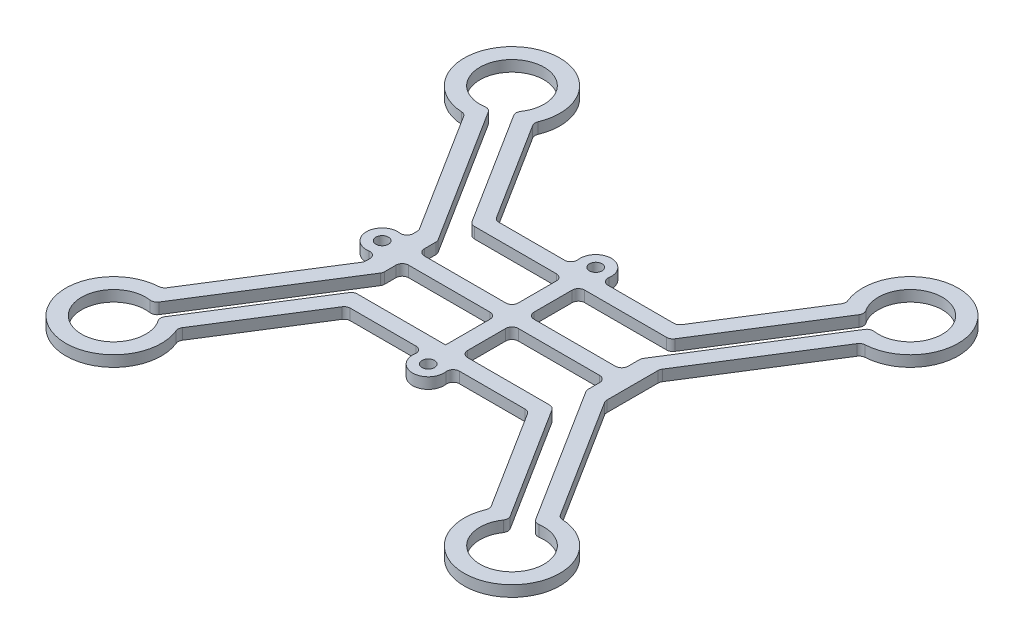
SolidWorks part; units mm, degrees
material "Hexcel AS4C (3000 Filaments)"
ref_plane "Front Plane" through (0, 0, 0) normal (0, 0, 1) x (1, 0, 0)
ref_plane "Top Plane" through (0, 0, 0) normal (0, 1, 0) x (1, 0, 0)
ref_plane "Right Plane" through (0, 0, 0) normal (1, 0, 0) x (0, 0, -1)
sketch "Sketch1" plane through (0, 0, 0) normal (0, 1, 0) x (1, 0, 0)
  line L0 (0, 28.7416) -> (0, -31.95) construction
  line L1 (-19.25, 11.875) -> (19.25, 11.875)
  line L2 (-19.25, 11.875) -> (-19.25, -11.875)
  line L3 (-19.25, -11.875) -> (19.25, -11.875)
  line L4 (19.25, 11.875) -> (19.25, -11.875)
  line L5 (-19.25, 11.875) -> (19.25, -11.875) construction
  line L6 (-19.25, -11.875) -> (19.25, 11.875) construction
  line L7 (-23.7954, 0) -> (45.7192, 0) construction
  line L8 (-31.8198, 4.3198) -> (-31.8198, -4.3198) construction
  line L9 (-31.8198, -31.8198) -> (-31.8198, 31.8198) construction
  line L10 (-31.8198, 31.8198) -> (-19.25, 11.875) construction
  line L11 (19.25, 9.825) -> (-13.5, 9.825)
  line L12 (19.25, 9.825) -> (19.25, -9.825)
  line L13 (19.25, -9.825) -> (-13.5, -9.825)
  line L14 (-13.5, 9.825) -> (-13.5, -9.825)
  line L15 (19.25, 9.825) -> (-13.5, -9.825) construction
  line L16 (19.25, -9.825) -> (-13.5, 9.825) construction
  line L17 (-31.727, 24.1704) -> (-19.25, 4.3728)
  line L18 (-24.959, 28.4358) -> (-14.5219, 11.875)
  line L19 (-35.2038, 29.6871) -> (-22.634, 9.7423) construction
  line L20 (-28.4358, 33.9525) -> (-15.866, 14.0077) construction
  line L21 (24.959, 28.4358) -> (14.5219, 11.875)
  line L22 (31.727, 24.1704) -> (19.25, 4.3728)
  line L23 (24.959, -28.4358) -> (14.5219, -11.875)
  line L24 (31.727, -24.1704) -> (19.25, -4.3728)
  line L25 (-24.959, -28.4358) -> (-14.5219, -11.875)
  line L26 (-31.727, -24.1704) -> (-19.25, -4.3728)
  line L27 (-31.8198, 31.8198) -> (31.8198, 31.8198) construction
  circle A0 centre (-31.8198, 31.8198) radius 27.5
  circle A1 centre (31.8198, 31.8198) radius 27.5
  circle A2 centre (-31.8198, -31.8198) radius 27.5
  circle A3 centre (31.8198, -31.8198) radius 27.5
  circle A4 centre (-31.8198, 31.8198) radius 7.65
  circle A5 centre (-31.8198, 31.8198) radius 5.125
  circle A6 centre (31.8198, 31.8198) radius 5.125
  circle A7 centre (31.8198, 31.8198) radius 7.65
  circle A8 centre (31.8198, -31.8198) radius 5.125
  circle A9 centre (31.8198, -31.8198) radius 7.65
  circle A10 centre (-31.8198, -31.8198) radius 5.125
  circle A11 centre (-31.8198, -31.8198) radius 7.65
  point P0 (0, 0)
  point P18 (2.875, 0)
  dimension "D3" = 55
  dimension "D8" = 15.3
  dimension "D9" = 10.25
  dimension "D1" = 23.75
  dimension "D2" = 38.5
  dimension "D4" = 19.65
  dimension "D5" = 32.75
  dimension "D10" = 8
  dimension "D6" = 90
extrude "Boss-Extrude1" add sketch "Sketch1" along normal blind 1.75 contours A4 A5 | A4 L17 L2 L1 L18 | A11 A10 | L26 A11 L25 L3 L2 | A9 A8 | A9 L24 L4 L3 L23 | A7 A6 | L22 A7 L21 L1 L4 | L26 A2 L2 | A0 L17 L2 | A3 L24 L4 | L22 A1 L12 | L1 L4 L3 L2 region at (-23.128, 0, -17.8619) region at (-19.7311, 0, -6.1292) region at (-27.8564, 0, -25.5309) region at (-19.7311, 0, 6.1292) region at (23.128, 0, -17.8619) region at (-23.128, 0, 17.8619) region at (30.1315, 0, -39.0592) region at (19.7311, 0, -6.1292) region at (-27.8564, 0, 25.5309) region at (19.7311, 0, 6.1292) region at (23.128, 0, 17.8619) region at (27.8564, 0, 25.5309)
sketch "Sketch2" plane through (0, 1.75, 0) normal (0, 1, 0) x (1, 0, 0)
  line L0 (-19.25, 0) -> (19.25, 0) construction
  line L1 (-19.25, 4.3728) -> (-19.25, -4.3728) construction
  line L2 (19.25, 4.3728) -> (19.25, -4.3728) construction
  line L3 (0, 11.875) -> (0, -11.875) construction
  line L4 (-14.5219, 11.875) -> (14.5219, 11.875) construction
  line L5 (-14.5219, -11.875) -> (14.5219, -11.875) construction
  line L6 (-29.0873, 27.484) -> (-11.766, 0) construction
  line L7 (-31.727, 24.1704) -> (-19.25, 4.3728) construction
  line L8 (-24.959, 28.4358) -> (-14.5219, 11.875) construction
  line L9 (-30.4507, 26.881) -> (-16.2654, 4.3728)
  line L10 (-31.8198, 36.9448) -> (-31.8198, 39.4698) construction
  line L11 (-23.3581, 15.6269) -> (-25.4942, 14.2807) construction
  line L12 (-19.25, 4.3728) -> (19.25, 4.3728) construction
  line L13 (-27.955, 28.4539) -> (-12.7784, 4.3728)
  line L14 (-15.9152, 9.35) -> (15.9152, 9.35)
  line L15 (0, 9.35) -> (0, 11.875) construction
  line L16 (-16.2654, 4.3728) -> (-16.2654, -4.3728)
  line L17 (-12.7784, 4.3728) -> (-12.7784, -4.3728)
  line L18 (12.7784, 4.3728) -> (12.7784, -4.3728)
  line L19 (16.2654, 4.3728) -> (16.2654, -4.3728)
  line L20 (27.955, 28.4539) -> (12.7784, 4.3728)
  line L21 (30.4507, 26.881) -> (16.2654, 4.3728)
  line L22 (27.955, -28.4539) -> (12.7784, -4.3728)
  line L23 (30.4507, -26.881) -> (16.2654, -4.3728)
  line L24 (-15.9152, -9.35) -> (15.9152, -9.35)
  line L25 (-30.4507, -26.881) -> (-16.2654, -4.3728)
  line L26 (-27.955, -28.4539) -> (-12.7784, -4.3728)
  line L27 (-1.2625, 0) -> (1.2625, 0) construction
  line L28 (1.2625, -9.35) -> (-1.2625, -9.35)
  line L29 (1.2625, -9.35) -> (1.2625, 9.35)
  line L30 (1.2625, 9.35) -> (-1.2625, 9.35)
  line L31 (-1.2625, -9.35) -> (-1.2625, 9.35)
  line L32 (1.2625, -9.35) -> (-1.2625, 9.35) construction
  line L33 (1.2625, 9.35) -> (-1.2625, -9.35) construction
  line L35 (-16.2654, -1.2625) -> (16.2654, -1.2625)
  line L36 (-16.2654, -1.2625) -> (-16.2654, 1.2625)
  line L37 (-16.2654, 1.2625) -> (16.2654, 1.2625)
  line L38 (16.2654, -1.2625) -> (16.2654, 1.2625)
  line L39 (-16.2654, -1.2625) -> (16.2654, 1.2625) construction
  line L40 (-16.2654, 1.2625) -> (16.2654, -1.2625) construction
  circle A0 centre (-31.8198, 31.8198) radius 5.125 construction
  circle A1 centre (-31.8198, 31.8198) radius 5.125
  circle A2 centre (31.8198, 31.8198) radius 5.125
  arc A3 (-24.959, 28.4358) -> (-31.727, 24.1704) centre (-31.8198, 31.8198) ccw construction
  circle A4 centre (-31.8198, -31.8198) radius 5.125
  circle A5 centre (31.8198, -31.8198) radius 5.125
  point P39 (0, 0)
  point P41 (0, 0)
  point P42 (-16.2654, 0)
  point P45 (12.7784, 0)
  point P47 (0, 9.35)
  point P60 (16.2654, 0)
  point P66 (-12.7784, 0)
extrude "Cut-Extrude2" cut sketch "Sketch2" against normal up to next contours L16 L37 L17 L13 L33 L9 | L17 L37 L31 L14 L13 | L29 L37 L18 L20 L14 | L18 L37 L19 L21 L36 L20 | L35 L18 L22 L23 L19 | L35 L29 L24 L22 L18 | L35 L17 L26 L24 L31 | L35 L16 L25 L32 L26 L17 region at (-20.9447, 1.75, -14.4076) region at (-7.5466, 1.75, -5.4907) region at (-20.9447, 1.75, 14.4076) region at (-7.5466, 1.75, 5.4907) region at (7.5466, 1.75, -5.4907) region at (20.9447, 1.75, -14.4076) region at (7.5466, 1.75, 5.4907) region at (20.9447, 1.75, 14.4076)
fillet "Fillet1" radius 1 43 edges at (-30.4507, 0.875, 26.881) (-31.727, 0.875, -24.1704) (-1.2625, 0.875, -1.2625) (1.2625, 0.875, -1.2625) (-16.2654, 0.875, -1.2625) (-1.2625, 0.875, 1.2625) (-1.2625, 0.875, -9.35) (-31.727, 0.875, 24.1704) (-19.25, 0.875, 4.3728) (-19.25, 0.875, -4.3728) (24.959, 0.875, -28.4358) (-27.955, 0.875, -28.4539) (-27.955, 0.875, 28.4539) (-14.5219, 0.875, -11.875) (-15.9152, 0.875, 9.35) (-30.4507, 0.875, -26.881) (-24.959, 0.875, -28.4358) (-15.9152, 0.875, -9.35) (-16.2654, 0.875, -4.3728) (-16.2654, 0.875, 4.3728) (-16.2654, 0.875, 1.2625) (1.2625, 0.875, -9.35) (1.2625, 0.875, 1.2625) (1.2625, 0.875, 9.35) (16.2654, 0.875, -1.2625) (16.2654, 0.875, -4.3728) (15.9152, 0.875, -9.35) (14.5219, 0.875, -11.875) (30.4507, 0.875, -26.881) (27.955, 0.875, -28.4539) (31.727, 0.875, -24.1704) (19.25, 0.875, -4.3728) (16.2654, 0.875, 1.2625) (16.2654, 0.875, 4.3728) (15.9152, 0.875, 9.35) (19.25, 0.875, 4.3728) (31.727, 0.875, 24.1704) (30.4507, 0.875, 26.881) (27.955, 0.875, 28.4539) (24.959, 0.875, 28.4358) (14.5219, 0.875, 11.875) (-14.5219, 0.875, 11.875) (-24.959, 0.875, 28.4358)
sketch "Sketch4" plane through (0, 0, 0) normal (0, -1, 0) x (1, 0, 0)
  line L0 (-28.6014, 0) -> (31.9252, 0) construction
  line L1 (0, -23.8326) -> (0, 22.253) construction
  line L2 (-13.9701, -11.875) -> (13.9701, -11.875) construction
  line L3 (-0.866, -11.875) -> (-1.7321, -13.375)
  line L4 (-1.7321, -13.375) -> (-0.866, -14.875)
  line L5 (-0.866, -14.875) -> (0.866, -14.875)
  line L6 (0.866, -14.875) -> (1.7321, -13.375)
  line L7 (1.7321, -13.375) -> (0.866, -11.875)
  line L8 (0.866, -11.875) -> (-0.866, -11.875)
  line L9 (-2.5, -13.375) -> (-2.5, -11.875) construction
  line L10 (-20.75, -2.5) -> (-19.25, -2.5) construction
  line L11 (-19.25, -4.084) -> (-19.25, 4.084) construction
  circle A0 centre (0, -13.375) radius 1
  circle A1 centre (0, -13.375) radius 2.5
  circle A2 centre (0, -13.375) radius 1.5 construction
  circle A3 centre (0, 13.375) radius 2.5
  circle A4 centre (0, 13.375) radius 1
  circle A5 centre (-20.75, 0) radius 1
  circle A6 centre (-20.75, 0) radius 2.5
  circle A7 centre (20.75, 0) radius 1
  circle A8 centre (20.75, 0) radius 2.5
  dimension "D1" = 2
  dimension "D2" = 5
  dimension "D3" = 3
extrude "Boss-Extrude2" add sketch "Sketch4" against normal up to surface (1.75 mm away) contours A6 A5 | A1 L8 L7 L6 L5 L4 L3 | L7 L8 L3 L4 L5 L6 A0 | A3 A4 region at (0, 0, -11.9208) region at (-2.4293, 0, -13.375) region at (-2.4293, 0, 13.375) region at (-23.1793, 0, 0) up to face at (16.0204, 1.75, -12.188)
fillet "Fillet2" radius 1 6 edges at (-2, 0.875, 11.875) (2, 0.875, 11.875) (2, 0.875, -11.875) (-2, 0.875, -11.875) (-19.25, 0.875, -2) (-19.25, 0.875, 2)
equation "\"PropDiameter\"=55"
equation "\"D3@Sketch1\"=\"PropDiameter\""
